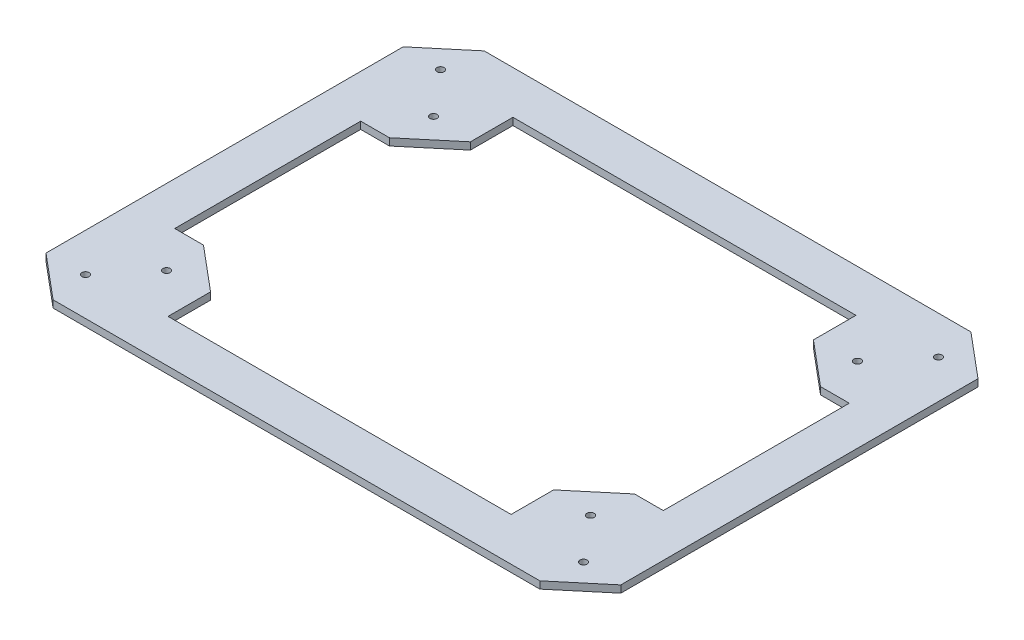
SolidWorks part; units mm, degrees
material "Thornel Mat VMA"
ref_plane "Front Plane" through (0, 0, 0) normal (0, 0, 1) x (1, 0, 0)
ref_plane "Top Plane" through (0, 0, 0) normal (0, 1, 0) x (1, 0, 0)
ref_plane "Right Plane" through (0, 0, 0) normal (1, 0, 0) x (0, 0, -1)
sketch "Sketch1" plane through (0, 0, 0) normal (0, 1, 0) x (1, 0, 0)
  line L0 (-127, 78.9232) -> (-107.5425, 95.25)
  line L1 (-127, -95.25) -> (127, -95.25)
  line L2 (-127, -95.25) -> (-127, 95.25)
  line L3 (-127, 95.25) -> (127, 95.25)
  line L4 (127, -95.25) -> (127, 95.25)
  line L5 (-107.95, 41.085) -> (-107.95, -41.085)
  line L8 (-107.95, 41.085) -> (-95.25, 41.085)
  line L10 (-127, 95.25) -> (127, -95.25) construction
  line L12 (127, 78.9232) -> (107.5425, 95.25)
  line L14 (75.7925, 57.4118) -> (75.7925, 76.2)
  line L15 (95.25, 41.085) -> (75.7925, 57.4118)
  line L16 (107.95, 41.085) -> (95.25, 41.085)
  line L17 (107.95, 41.085) -> (107.95, -41.085)
  line L18 (127, -78.9232) -> (107.5425, -95.25)
  line L19 (107.95, -41.085) -> (95.25, -41.085)
  line L20 (95.25, -41.085) -> (75.7925, -57.4118)
  line L21 (75.7925, -57.4118) -> (75.7925, -76.2)
  line L22 (127, 0) -> (-127, 0) construction
  line L23 (0, -13.6985) -> (0, 95.25) construction
  line L25 (-75.7925, -76.2) -> (75.7925, -76.2)
  line L26 (-75.7925, -57.4118) -> (-75.7925, -76.2)
  line L27 (-95.25, 41.085) -> (-127, 78.9232) construction
  line L28 (-95.25, 41.085) -> (-75.7925, 57.4118)
  line L29 (-75.7925, 57.4118) -> (-75.7925, 76.2)
  line L30 (-75.7925, 76.2) -> (75.7925, 76.2)
  line L31 (-95.25, -41.085) -> (-75.7925, -57.4118)
  line L32 (-107.95, -41.085) -> (-95.25, -41.085)
  line L33 (-127, -78.9232) -> (-107.5425, -95.25)
  line L34 (-75.7925, 57.4118) -> (-107.5425, 95.25) construction
  point P0 (0, 0)
  point P1 (0, 0)
  point P14 (0, 0)
  point P22 (0, 76.2)
  point P33 (107.95, 0)
  point P41 (0, 0)
  point P44 (-107.95, 0)
  dimension "D1" = 190.5
  dimension "D2" = 254
  dimension "D3" = 19.05
  dimension "D4" = 19.05
  dimension "D5" = 40
  dimension "D6" = 25.4
  dimension "D7" = 12.7
extrude "Boss-Extrude1" add sketch "Sketch1" along normal blind 3.175 contours L2 L1 L4 L3 L8 region at (-115.2304, 0, -84.6544)
sketch "Sketch2" plane through (0, 3.175, 0) normal (0, 1, 0) x (1, 0, 0)
  line L0 (-85.5212, 49.2484) -> (-117.2712, 87.0866) construction
  line L1 (-95.25, 41.085) -> (-75.7925, 57.4118) construction
  line L2 (-127, 78.9232) -> (-107.5425, 95.25) construction
  line L3 (0, 0) -> (0, 95.25) construction
  line L4 (-107.5425, 95.25) -> (107.5425, 95.25) construction
  line L5 (0, 0) -> (-127, 0) construction
  line L6 (-127, -78.9232) -> (-127, 78.9232) construction
  circle A0 centre (-93.6846, 58.9772) radius 1.5875
  circle A1 centre (-110.0114, 78.4347) radius 1.5875
  circle A2 centre (110.0114, 78.4347) radius 1.5875
  circle A3 centre (93.6846, 58.9772) radius 1.5875
  circle A4 centre (110.0114, -78.4347) radius 1.5875
  circle A5 centre (93.6846, -58.9772) radius 1.5875
  circle A6 centre (-110.0114, -78.4347) radius 1.5875
  circle A7 centre (-93.6846, -58.9772) radius 1.5875
  dimension "D2" = 3.175
  dimension "D3" = 3.175
  dimension "D1" = 25.4
  dimension "D4" = 12.7
extrude "Cut-Extrude1" cut sketch "Sketch2" against normal through all
